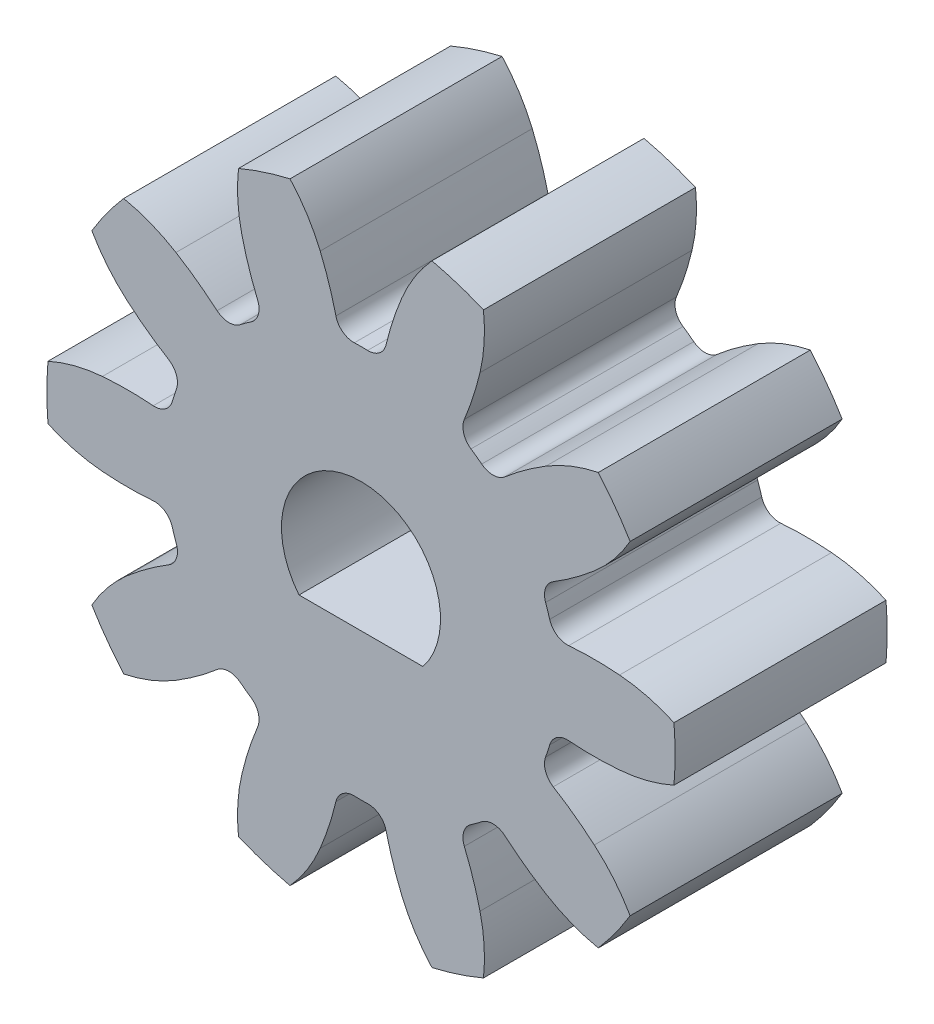
SolidWorks part; units mm, degrees
material "Plain Carbon Steel"
ref_plane "Front" through (0, 0, 0) normal (0, 0, 1) x (1, 0, 0)
ref_plane "Top" through (0, 0, 0) normal (0, 1, 0) x (1, 0, 0)
ref_plane "Right" through (0, 0, 0) normal (1, 0, 0) x (0, 0, -1)
sketch "Sketch1" plane through (0, 0, 0) normal (0, 0, 1) x (1, 0, 0)
  line L0 (0, 0) -> (4.9389, 0) construction
  line L1 (4.9389, 0) -> (5.9267, 0) construction
  circle A0 centre (0, 0) radius 4.9389 construction
  circle A1 centre (0, 0) radius 5.9267
  dimension "pitch_diameter" = 9.8778
  dimension "addendum" = 0.9878
extrude "BLANK DISK" add sketch "Sketch1" along normal mid plane 4
sketch "Sketch2" plane through (0, 0, 2) normal (0, 0, 1) x (1, 0, 0)
  line L0 (0, 0) -> (3.7042, 0) construction
  line L1 (3.7042, 0) -> (4.9389, 0) construction
  line L2 (0, 0) -> (-5.9267, 0) construction
  line L3 (0, 0) -> (-4.7948, -3.4836) construction
  line L4 (-5.0773, -3.0572) -> (-4.4021, -2.2392) construction
  line L5 (-4.4021, -2.2392) -> (-3.386, -1.502) construction
  line L6 (-5.9046, -0.511) -> (-4.8776, -0.7759) construction
  line L7 (-4.8776, -0.7759) -> (-3.6222, -0.7751) construction
  line L8 (-3.946, -2.867) -> (-4.4021, -2.2392) construction
  line L9 (-4.8776, -0.7759) -> (-4.8776, 0) construction
  line L12 (0, 0) -> (-4.8776, -0.7759) construction
  line L13 (0, 0) -> (-4.4021, -2.2392) construction
  line L14 (-4.4021, -2.2392) -> (-2.9167, -5.1593) construction
  line L15 (-4.8776, -0.7759) -> (-5.3922, 2.4595) construction
  line L16 (-4.4021, -2.2392) -> (-4.8776, -0.7759) construction
  line L17 (-3.5229, -1.1447) -> (-3.6222, -0.7751) construction
  line L18 (-3.5229, -1.1447) -> (-3.386, -1.502) construction
  circle A0 centre (0, 0) radius 4.9389 construction
  circle A1 centre (0, 0) radius 3.7042 construction
  circle A2 centre (0, 0) radius 5.9267 construction
  arc A3 (-5.0773, -3.0572) -> (-5.9046, -0.511) centre (0, 0) cw
  arc A4 (-3.386, -1.502) -> (-3.6222, -0.7751) centre (0, 0) cw construction
  arc A6 (-5.0773, -3.0572) -> (-4.4021, -2.2392) centre (-2.3814, -4.5949) cw
  arc A7 (-5.9046, -0.511) -> (-4.8776, -0.7759) centre (-4.6274, 2.3176) ccw
  arc A8 (-4.4021, -2.2392) -> (-3.627, -1.6756) centre (-0.5094, -6.7773) cw
  arc A9 (-4.8776, -0.7759) -> (-3.9192, -0.7763) centre (-4.3957, 5.1836) ccw
  arc A10 (-3.627, -1.6756) -> (-3.4823, -1.2627) centre (-3.8073, -1.3806) ccw
  arc A11 (-3.9192, -0.7763) -> (-3.5594, -1.0253) centre (-3.8917, -1.121) cw
  arc A12 (-3.4823, -1.2627) -> (-3.5594, -1.0253) centre (0, 0) cw
  dimension "D12" = 3.1036
  dimension "D3" = 36
  dimension "D4" = 0.7759
  dimension "D5" = 0.7759
  dimension "D11" = 1.5387
  dimension "D14" = 9
  dimension "D15" = 9
  dimension "base_fillet" = 0.3457
  dimension "pitch_diameter" = 9.8778
  dimension "deddendum" = 1.2347
extrude "GEAR TOOTH CUT" cut sketch "Sketch2" against normal through all
ref_axis "CENTER AXIS" through (0, 0, 50) along (0, 0, -1)
pattern_circular "GEAR TEETH REVOLVE" count 10 over 360 about axis through (0, 0, 50) along (0, 0, -1) of "GEAR TOOTH CUT"
sketch "Sketch4" plane through (0, 0, 2) normal (0, 0, 1) x (1, 0, 0)
  circle A0 centre (0, 0) radius 0.75
  dimension "D1" = 1.5
extrude "Hub Extrude" add sketch "Sketch4" along normal blind 0.635
sketch "Sketch3" plane through (0, 0, 2) normal (0, 0, 1) x (1, 0, 0)
  line L0 (-1.1689, -0.94) -> (1.1689, -0.94)
  arc A0 (1.1689, -0.94) -> (-1.1689, -0.94) centre (0, 0) ccw
  dimension "D1" = 3
  dimension "D2" = 0.94
extrude "HEX BORE CUT" cut sketch "Sketch3" against normal through all and the other way through all
equation "\"N_teeth\"= 10.000000"
equation "\"pitch_diameter\"= 140 / 360"
equation "\"Pd\"=\"N_teeth\"/\"pitch_diameter\""
equation "\"addendum\"=1.000/\"Pd\""
equation "\"face_width\"= 4mm"
equation "\"deddendum\"=1.250/\"Pd\""
equation "\"D3@Sketch2\" = 360/\"N_teeth\""
equation "\"tooth_thickness\"=1.571/\"Pd\""
equation "\"D4@Sketch2\" = \"tooth_thickness\"/2"
equation "\"D5@Sketch2\" = \"tooth_thickness\"/2"
equation "\"Pressure_Angle\"=14.500000"
equation "\"base_fillet\"=0.35/\"Pd\""
equation "\"D12@Sketch2\" = 2*\"tooth_thickness\""
equation "\"hub_diameter\"= 1.5mm"
equation "\"bore\"= 0.125000"
equation "\"hub_projection\"=0.250000"
equation "\"sss_diam\"=0.062500"
